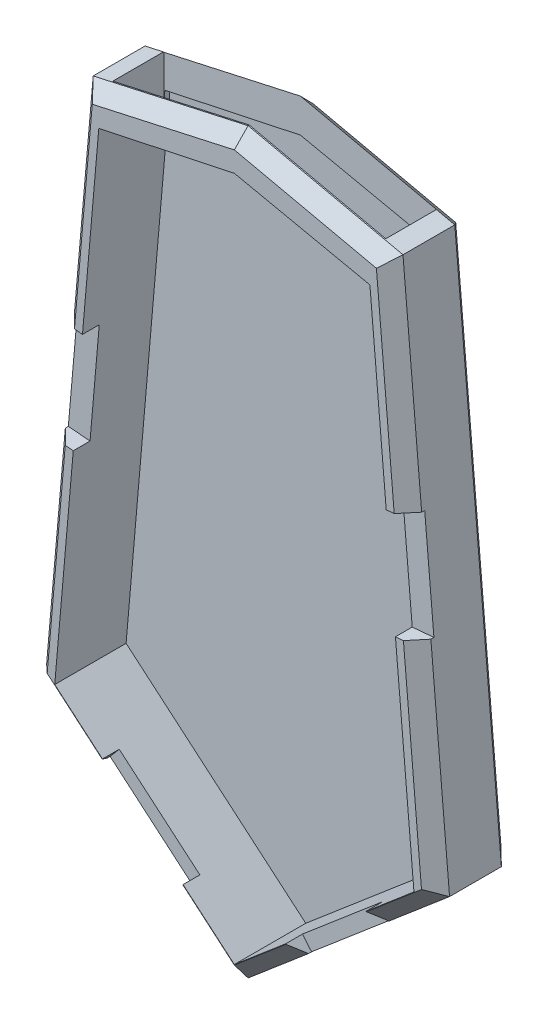
SolidWorks part; units mm, degrees
ref_plane "Front Plane" through (0, 0, 0) normal (0, 0, 1) x (1, 0, 0)
ref_plane "Top Plane" through (0, 0, 0) normal (0, 1, 0) x (1, 0, 0)
ref_plane "Right Plane" through (0, 0, 0) normal (1, 0, 0) x (0, 0, -1)
sketch "Sketch1" plane through (0, 0, 0) normal (0, 0, 1) x (1, 0, 0)
  line L3 (-20.9408, 106.9697) -> (-20.9408, -45.2232) construction
  line L4 (-59.0408, -0.235) -> (-20.9408, -32.6139)
  line L5 (-20.9408, -32.6139) -> (17.1592, -0.235)
  line L6 (-59.0408, -0.235) -> (-50.2297, 100.4765)
  line L7 (-50.2297, 100.4765) -> (-20.9408, 106.9697)
  line L8 (-59.0408, -0.235) -> (17.1592, -0.235) construction
  line L9 (-20.9408, 106.9697) -> (8.348, 100.4765)
  line L10 (8.348, 100.4765) -> (17.1592, -0.235)
  line L11 (-50.2297, 100.4765) -> (17.1592, -0.235) construction
  line L13 (-59.0408, -0.235) -> (8.348, 100.4765) construction
  line L15 (-46.5746, 95.014) -> (-20.9408, 100.4765)
  line L16 (-20.9408, 100.4765) -> (4.6929, 95.014)
  line L17 (4.6929, 95.014) -> (13.0261, -0.235)
  line L18 (13.0261, -0.235) -> (-20.9408, -29.1015)
  line L19 (-20.9408, -29.1015) -> (-54.9078, -0.235)
  line L20 (-54.9078, -0.235) -> (-46.5746, 95.014)
  dimension "D1" = 76.2
  dimension "D2" = 30
  dimension "D3" = 30
  dimension "D4" = 155
  dimension "D5" = 50
  dimension "D6" = 50
  dimension "D7" = 85
  dimension "D8" = 85
  dimension "D9" = 0
  dimension "D10" = 0
  dimension "D11" = 360
  dimension "D12" = 360
  dimension "D13" = 95.6128
  dimension "D14" = 44.576
  dimension "D15" = 107.03
  dimension "D16" = 107.03
  dimension "D17" = 26.2093
  dimension "D18" = 26.2093
  dimension "D19" = 95.6128
  dimension "D20" = 44.576
  dimension "D21" = 129.578
  dimension "D22" = 99.282
extrude "Boss-Extrude1" add sketch "Sketch1" along normal blind 15
extrude "Boss-Extrude2" add sketch "Sketch1<6>" along normal blind 1.5 contours L20 L19 L18 L17 L16 L15 region at (-20.9408, 38.2967, 0)
sketch "Sketch1<6>" plane through (0, 0, 0) normal (0, 0, 1) x (1, 0, 0) same geometry as "Sketch1"
sketch "Sketch4" plane through (0, 0, 0) normal (0, 1, 0) x (1, 0, 0)
  line L0 (-20.9408, 0) -> (-50.2297, 0) construction
  line L1 (-46.7528, -2.5) -> (4.8711, -2.5)
  line L2 (-46.7528, -2.5) -> (-46.7528, -12.1724)
  line L3 (-46.7528, -12.1724) -> (4.8711, -12.1724)
  line L4 (4.8711, -2.5) -> (4.8711, -12.1724)
  line L5 (-54.9078, -15) -> (-54.9078, -1.5) construction
  line L6 (13.0261, -15) -> (13.0261, -1.5) construction
  dimension "D1" = 2.5
  dimension "D2" = 8.155
  dimension "D3" = 8.155
extrude "Cut-Extrude2" cut sketch "Sketch4" along normal blind 144.5
sketch "Sketch6" plane through (17.0084, 1.488, 0) normal (0.9962, 0.0872, 0) x (0, 0, -1)
  line L0 (-15, -1.7297) -> (-15, 99.3666) construction
  line L1 (-15, 58.8203) -> (-11.825, 58.8203)
  line L2 (-15, 58.8203) -> (-15, 38.8203)
  line L3 (-15, 38.8203) -> (-11.825, 38.8203)
  line L4 (-11.825, 58.8203) -> (-11.825, 38.8203)
  line L6 (-15, -1.7297) -> (0, -1.7297) construction
  dimension "D1" = 3.175
  dimension "D2" = 20
  dimension "D3" = 40.55
sketch "Sketch7" plane through (-58.5719, 5.1244, 0) normal (-0.9962, 0.0872, 0) x (0, 0, 1)
  line L0 (15, 95.7164) -> (15, -5.3799) construction
  line L1 (15, 55.1701) -> (11.825, 55.1701)
  line L2 (15, 55.1701) -> (15, 35.1701)
  line L3 (15, 35.1701) -> (11.825, 35.1701)
  line L4 (11.825, 55.1701) -> (11.825, 35.1701)
  line L5 (15, -5.3799) -> (0, -5.3799) construction
  dimension "D1" = 3.175
  dimension "D2" = 20
  dimension "D3" = 40.55
sketch "Sketch8" plane through (-24.8751, -29.2704, 0) normal (-0.6476, -0.762, 0) x (0.762, -0.6476, 0)
  line L0 (-44.8369, 15) -> (5.1631, 15) construction
  line L1 (-29.8369, 15) -> (-9.8369, 15)
  line L2 (-29.8369, 15) -> (-29.8369, 11.825)
  line L3 (-29.8369, 11.825) -> (-9.8369, 11.825)
  line L4 (-9.8369, 15) -> (-9.8369, 11.825)
  line L5 (-44.8369, 15) -> (-44.8369, 0) construction
  dimension "D1" = 3.175
  dimension "D2" = 20
  dimension "D3" = 15
sketch "Sketch9" plane through (7.3118, -8.6037, 0) normal (0.6476, -0.762, 0) x (0.762, 0.6476, 0)
  line L0 (-37.0769, 15) -> (12.9231, 15) construction
  line L1 (-22.0769, 15) -> (-2.0769, 15)
  line L2 (-22.0769, 15) -> (-22.0769, 11.825)
  line L3 (-22.0769, 11.825) -> (-2.0769, 11.825)
  line L4 (-2.0769, 15) -> (-2.0769, 11.825)
  line L5 (12.9231, 15) -> (12.9231, 0) construction
  dimension "D1" = 15
  dimension "D2" = 20
  dimension "D3" = 3.175
extrude "Cut-Extrude3" cut sketch "Sketch9" against normal blind 5.5
extrude "Cut-Extrude4" cut sketch "Sketch6" against normal blind 5.5
extrude "Cut-Extrude5" cut sketch "Sketch8" against normal blind 5.5
extrude "Cut-Extrude6" cut sketch "Sketch7" against normal blind 5.5
chamfer "Chamfer1" distance 2.6 angle 45 16 edges at (-35.5853, 103.7231, 0) (-6.2964, 103.7231, 0) (-54.6353, 50.1207, 0) (-39.9908, -16.4245, 0) (-1.8908, -16.4245, 0) (12.7536, 50.1207, 0) (-15.2258, -27.7571, 15) (-26.6558, -27.7571, 15) (-53.3258, -5.0919, 15) (-57.2738, 19.9628, 15) (-51.9966, 80.2805, 15) (-35.5853, 103.7231, 15) (-6.2964, 103.7231, 15) (10.115, 80.2805, 15) (11.4442, -5.0919, 15) (15.3921, 19.9628, 15)
